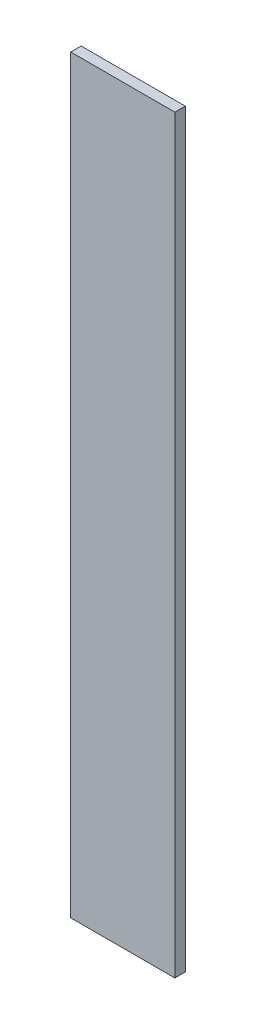
SolidWorks part; units mm, degrees
material "Acrylic (Medium-high impact)"
ref_plane "Front Plane" through (0, 0, 0) normal (0, 0, 1) x (1, 0, 0)
ref_plane "Top Plane" through (0, 0, 0) normal (0, 1, 0) x (1, 0, 0)
ref_plane "Right Plane" through (0, 0, 0) normal (1, 0, 0) x (0, 0, -1)
sketch "Sketch1" plane through (0, 0, 0) normal (0, 1, 0) x (1, 0, 0)
  line L1 (15.875, -1.5875) -> (-15.875, -1.5875)
  line L2 (15.875, -1.5875) -> (15.875, 1.5875)
  line L3 (15.875, 1.5875) -> (-15.875, 1.5875)
  line L4 (-15.875, -1.5875) -> (-15.875, 1.5875)
  line L5 (15.875, -1.5875) -> (-15.875, 1.5875) construction
  line L6 (15.875, 1.5875) -> (-15.875, -1.5875) construction
  point P0 (0, 0)
  dimension "D1" = 3.175
  dimension "D2" = 31.75
extrude "Boss-Extrude1" add sketch "Sketch1" along normal blind 228.6
sketch "Sketch2" plane through (0, 0, 1.5875) normal (0, 0, 1) x (1, 0, 0)
  line L1 (-15.875, 228.6) -> (15.875, 228.6)
  line L2 (-15.875, 228.6) -> (-15.875, 0)
  line L3 (-15.875, 0) -> (15.875, 0)
  line L4 (15.875, 228.6) -> (15.875, 0)
